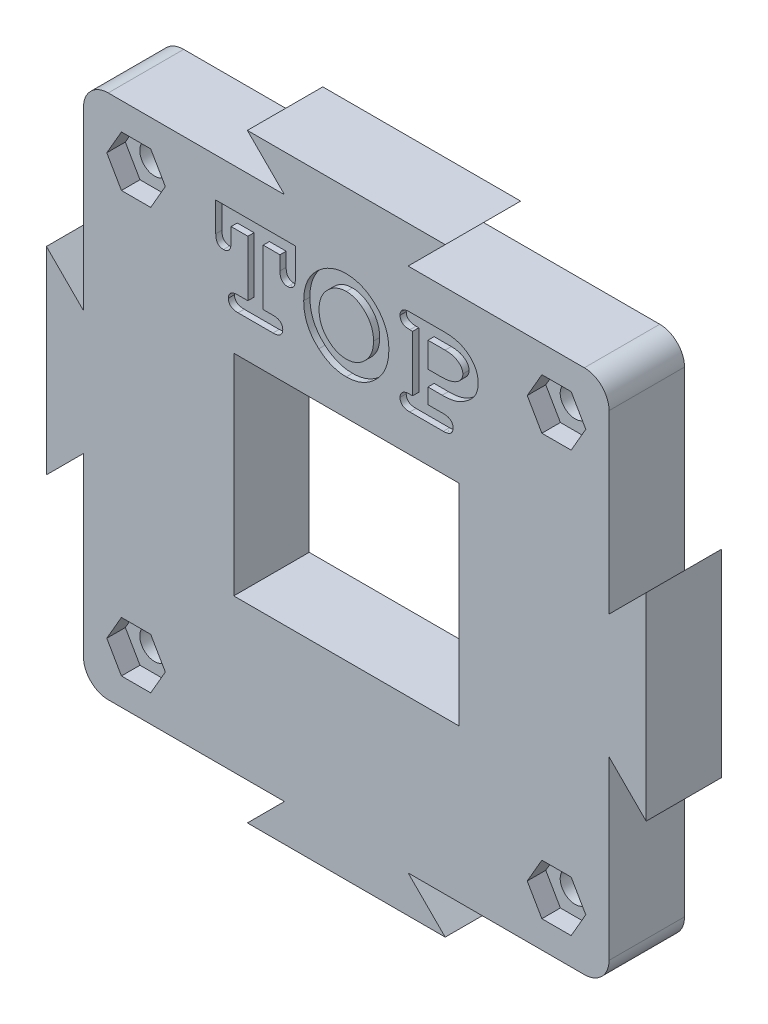
SolidWorks part; units mm, degrees
ref_plane "Front Plane" through (0, 0, 0) normal (0, 0, 1) x (1, 0, 0)
ref_plane "Top Plane" through (0, 0, 0) normal (0, 1, 0) x (1, 0, 0)
ref_plane "Right Plane" through (0, 0, 0) normal (1, 0, 0) x (0, 0, -1)
sketch "Sketch1" plane through (0, 0, 0) normal (0, 0, 1) x (1, 0, 0)
  line L4 (-5, 21.25) -> (-19.25, 21.25)
  line L5 (-5, 21.25) -> (-19.25, 21.25)
  line L6 (-21.25, 19.25) -> (-21.25, 5)
  line L7 (-21.25, 19.25) -> (-21.25, 5)
  line L21 (-8.9, -8.7) -> (8.9, -8.7) construction
  line L22 (-8.9, 7.9) -> (-8.9, -8.7) construction
  line L23 (8.9, 7.9) -> (-8.9, 7.9) construction
  line L24 (8.9, -8.7) -> (8.9, 7.9) construction
  line L25 (-8.9, -8.7) -> (8.9, -8.7) construction
  line L26 (-8.9, 7.9) -> (-8.9, -8.7) construction
  line L27 (8.9, 7.9) -> (-8.9, 7.9) construction
  line L28 (8.9, -8.7) -> (8.9, 7.9) construction
  line L29 (-9.1, -8.9) -> (9.1, -8.9)
  line L30 (9.1, -8.9) -> (9.1, 8.1)
  line L31 (9.1, 8.1) -> (-9.1, 8.1)
  line L32 (-9.1, 8.1) -> (-9.1, -8.9)
  line L50 (-21.25, 5) -> (-24.25, 8)
  line L51 (-21.25, 5) -> (-24.25, 8)
  line L52 (-24.25, 8) -> (-24.25, -8)
  line L53 (-24.25, 8) -> (-24.25, -8)
  line L54 (-24.25, -8) -> (-21.25, -5)
  line L55 (-24.25, -8) -> (-21.25, -5)
  line L56 (-21.25, -5) -> (-21.25, -19.25)
  line L57 (-21.25, -5) -> (-21.25, -19.25)
  line L58 (-19.25, -21.25) -> (-5, -21.25)
  line L59 (-19.25, -21.25) -> (-5, -21.25)
  line L60 (-5, -21.25) -> (-8, -24.25)
  line L61 (-5, -21.25) -> (-8, -24.25)
  line L62 (-8, -24.25) -> (8, -24.25)
  line L63 (-8, -24.25) -> (8, -24.25)
  line L64 (8, -24.25) -> (5, -21.25)
  line L65 (8, -24.25) -> (5, -21.25)
  line L66 (5, -21.25) -> (19.25, -21.25)
  line L67 (5, -21.25) -> (19.25, -21.25)
  line L68 (21.25, -19.25) -> (21.25, -5)
  line L69 (21.25, -19.25) -> (21.25, -5)
  line L70 (21.25, -5) -> (24.25, -8)
  line L71 (21.25, -5) -> (24.25, -8)
  line L72 (24.25, -8) -> (24.25, 8)
  line L73 (24.25, -8) -> (24.25, 8)
  line L74 (24.25, 8) -> (21.25, 5)
  line L75 (24.25, 8) -> (21.25, 5)
  line L76 (21.25, 5) -> (21.25, 19.25)
  line L77 (21.25, 5) -> (21.25, 19.25)
  line L78 (19.25, 21.25) -> (5, 21.25)
  line L79 (19.25, 21.25) -> (5, 21.25)
  line L80 (5, 21.25) -> (8, 24.25)
  line L81 (5, 21.25) -> (8, 24.25)
  line L82 (8, 24.25) -> (-8, 24.25)
  line L83 (8, 24.25) -> (-8, 24.25)
  line L84 (-8, 24.25) -> (-5, 21.25)
  line L85 (-8, 24.25) -> (-5, 21.25)
  circle A0 centre (-17, -17) radius 1.2 construction
  circle A1 centre (17, -17) radius 1.2 construction
  circle A2 centre (17, 17) radius 1.2 construction
  circle A3 centre (-17, 17) radius 1.2 construction
  arc A4 (-19.25, 21.25) -> (-21.25, 19.25) centre (-19.25, 19.25) ccw
  arc A5 (-19.25, 21.25) -> (-21.25, 19.25) centre (-19.25, 19.25) ccw
  arc A6 (-21.25, -19.25) -> (-19.25, -21.25) centre (-19.25, -19.25) ccw
  arc A7 (-21.25, -19.25) -> (-19.25, -21.25) centre (-19.25, -19.25) ccw
  circle A12 centre (-17, -17) radius 1.2
  circle A13 centre (17, -17) radius 1.2
  circle A14 centre (17, 17) radius 1.2
  circle A15 centre (-17, 17) radius 1.2
  arc A20 (19.25, -21.25) -> (21.25, -19.25) centre (19.25, -19.25) ccw
  arc A21 (19.25, -21.25) -> (21.25, -19.25) centre (19.25, -19.25) ccw
  arc A22 (21.25, 19.25) -> (19.25, 21.25) centre (19.25, 19.25) ccw
  arc A23 (21.25, 19.25) -> (19.25, 21.25) centre (19.25, 19.25) ccw
  dimension "D2" = 16
  dimension "D3" = 0.2
  dimension "D1" = 0
extrude "Boss-Extrude1" add sketch "Sketch1" along normal blind 6.1
sketch "Sketch2" plane through (0, 0, 0) normal (0, 0, -1) x (-1, 0, 0)
  line L0 (-9.5, 17) -> (9.5, 17) construction
  line L1 (-9.5, 18.25) -> (9.5, 18.25)
  line L2 (-9.5, 15.75) -> (9.5, 15.75)
  line L3 (-9.5, 16) -> (-9.5, 18) construction
  line L4 (9.5, 18) -> (9.5, 16) construction
  arc A0 (-9.5, 18.25) -> (-9.5, 15.75) centre (-9.5, 17) ccw
  arc A1 (9.5, 15.75) -> (9.5, 18.25) centre (9.5, 17) ccw
  point P2 (0, 17)
  point P7 (-17, 17)
  dimension "D1" = 2.5
extrude "Cut-Extrude3" cut sketch "Sketch2" against normal blind 1
sketch "Sketch3" plane through (0, 0, 6.1) normal (0, 0, 1) x (1, 0, 0)
  line L0 (-18.1836, -14.95) -> (-19.3671, -17)
  line L1 (15.8164, -14.95) -> (14.6329, -17)
  line L2 (14.6329, -17) -> (15.8164, -19.05)
  line L3 (15.8164, -19.05) -> (18.1836, -19.05)
  line L4 (18.1836, -19.05) -> (19.3671, -17)
  line L5 (19.3671, -17) -> (18.1836, -14.95)
  line L6 (18.1836, -14.95) -> (15.8164, -14.95)
  line L7 (-19.3671, -17) -> (-18.1836, -19.05)
  line L8 (-18.1836, -19.05) -> (-15.8164, -19.05)
  line L9 (-15.8164, -19.05) -> (-14.6329, -17)
  line L10 (-14.6329, -17) -> (-15.8164, -14.95)
  line L11 (-15.8164, -14.95) -> (-18.1836, -14.95)
  line L12 (-18.1836, 19.05) -> (-19.3671, 17)
  line L13 (-19.3671, 17) -> (-18.1836, 14.95)
  line L14 (-18.1836, 14.95) -> (-15.8164, 14.95)
  line L15 (-15.8164, 14.95) -> (-14.6329, 17)
  line L16 (-14.6329, 17) -> (-15.8164, 19.05)
  line L17 (-15.8164, 19.05) -> (-18.1836, 19.05)
  line L18 (15.8164, 19.05) -> (14.6329, 17)
  line L19 (14.6329, 17) -> (15.8164, 14.95)
  line L20 (15.8164, 14.95) -> (18.1836, 14.95)
  line L21 (18.1836, 14.95) -> (19.3671, 17)
  line L22 (19.3671, 17) -> (18.1836, 19.05)
  line L23 (18.1836, 19.05) -> (15.8164, 19.05)
  line L24 (15.8164, -14.95) -> (-18.1836, -14.95) construction
  line L25 (15.8164, -14.95) -> (15.8164, 19.05) construction
  circle A0 centre (17, -17) radius 2.05 construction
  circle A1 centre (-17, -17) radius 2.05 construction
  circle A2 centre (-17, 17) radius 2.05 construction
  circle A3 centre (17, 17) radius 2.05 construction
  dimension "D1" = 4.1
  dimension "D2" = 2
  dimension "D4" = 90
  dimension "D3" = 2
extrude "Cut-Extrude4" cut sketch "Sketch3" against normal blind 1.5
sketch "Sketch4" plane through (0, 0, 6.1) normal (0, 0, 1) x (1, 0, 0)
  line L0 (-21.25, 11.1) -> (21.25, 11.1) construction
  line L4 (-21.25, 19.25) -> (-21.25, 5) construction
  line L5 (21.25, 5) -> (21.25, 19.25) construction
  line L6 (9.1, 8.1) -> (-9.1, 8.1) construction
  text T0 "<b>TOP</b>" font "Courier New" height 7
  dimension "D1" = 3
extrude "Cut-Extrude5" cut sketch "Sketch4" against normal blind 0.5
